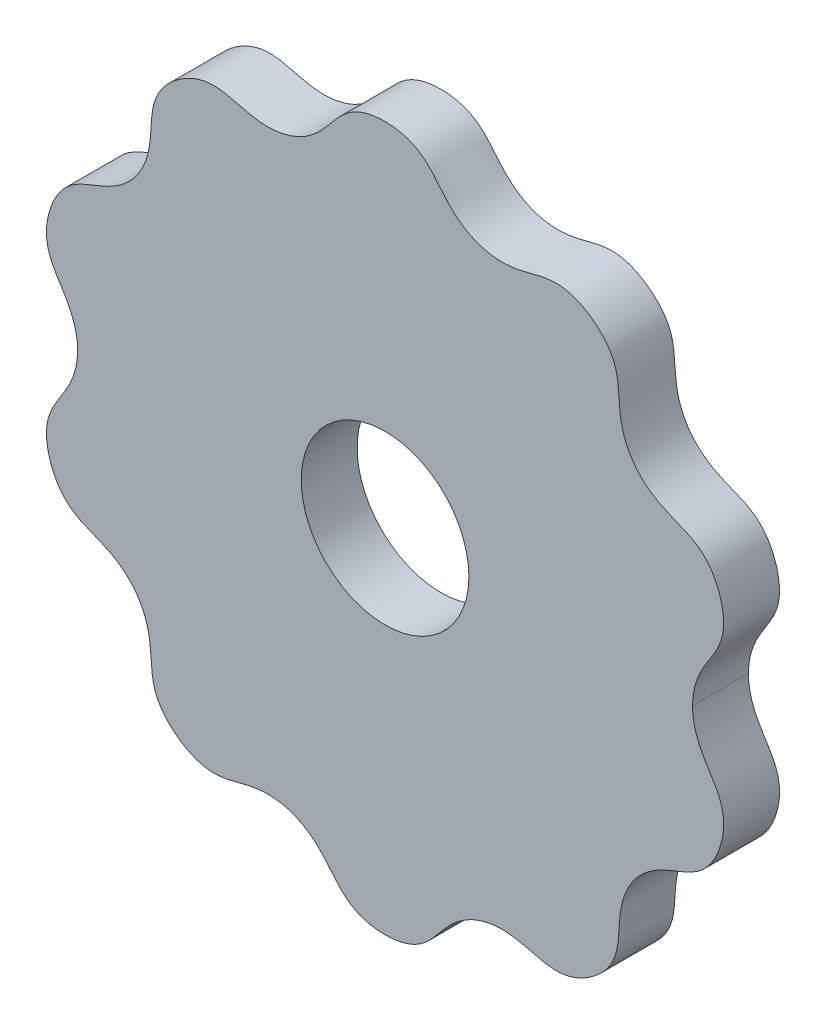
SolidWorks part; units mm, degrees
ref_plane "Front Plane" through (0, 0, 0) normal (0, 0, 1) x (1, 0, 0)
ref_plane "Top Plane" through (0, 0, 0) normal (0, 1, 0) x (1, 0, 0)
ref_plane "Right Plane" through (0, 0, 0) normal (1, 0, 0) x (0, 0, -1)
ref_plane "Plane1" through (0, 0, 4) normal (0, 0, 1) x (1, 0, 0)
sketch "Sketch1" plane through (0, 0, 4) normal (0, 0, 1) x (1, 0, 0)
  circle A0 centre (2, 0) radius 7.5
  spline S0 degree 5 poles (-25.5, 0) (-25.5, -0.5526) (-25.5746, -1.2434) (-25.8433, -2.3258) (-26.4239, -3.4504) (-27.2187, -4.6153) (-27.7942, -5.5576) (-28.2658, -6.8109) (-28.3864, -8.0323) (-28.1314, -9.4768) (-27.5806, -10.8552) (-26.8549, -11.8769) (-25.9559, -12.6827) (-24.9982, -13.1882) (-23.6912, -13.6755) (-22.3709, -14.191) (-20.8872, -15.2385) (-19.911, -16.4449) (-19.1799, -18.1084) (-18.9673, -19.4985) (-18.9256, -20.9082) (-18.8373, -22.0088) (-18.4822, -23.2999) (-17.8618, -24.3589) (-16.8065, -25.3777) (-15.5506, -26.1691) (-14.3631, -26.5691) (-13.162, -26.6926) (-12.0902, -26.5386) (-10.7464, -26.1646) (-9.3752, -25.8057) (-7.5591, -25.7809) (-6.0603, -26.1832) (-4.491, -27.0993) (-3.5019, -28.0989) (-2.6396, -29.2148) (-1.9213, -30.0534) (-0.8751, -30.8892) (0.2493, -31.3813) (1.7019, -31.5852) (3.183, -31.4872) (4.3789, -31.1128) (5.4232, -30.5068) (6.1999, -29.7522) (7.0672, -28.6597) (7.9654, -27.5634) (9.4202, -26.4759) (10.8692, -25.9204) (12.6772, -25.7391) (14.065, -25.9665) (15.4185, -26.3624) (16.4925, -26.6186) (17.8302, -26.6798) (19.0291, -26.417) (20.3241, -25.7282) (21.4648, -24.7783) (22.2122, -23.7725) (22.7008, -22.6684) (22.8857, -21.6014) (22.9452, -20.2078) (23.0275, -18.7929) (23.5652, -17.058) (24.4109, -15.7569) (25.7671, -14.5475) (27.0235, -13.9157) (28.3512, -13.4404) (29.3707, -13.0164) (30.4889, -12.2797) (31.3044, -11.3624) (31.9472, -10.0439) (32.3117, -8.605) (32.3252, -7.3519) (32.0715, -6.1715) (31.5938, -5.1996) (30.8229, -4.0372) (30.0578, -2.8441) (29.653, -1.6536) (29.5187, -0.829) (29.5, -0.1382) (29.5, 0) knots 0.5 0.5 0.5 0.5 0.5 0.5 0.513333 0.516667 0.526667 0.53 0.533333 0.54 0.55 0.556667 0.563333 0.566667 0.57 0.58 0.583333 0.596667 0.6 0.613333 0.616667 0.626667 0.63 0.633333 0.64 0.65 0.656667 0.663333 0.666667 0.67 0.68 0.683333 0.696667 0.7 0.713333 0.716667 0.726667 0.73 0.733333 0.74 0.75 0.756667 0.763333 0.766667 0.77 0.78 0.783333 0.796667 0.8 0.813333 0.816667 0.826667 0.83 0.833333 0.84 0.85 0.856667 0.863333 0.866667 0.87 0.88 0.883333 0.896667 0.9 0.913333 0.916667 0.926667 0.93 0.933333 0.94 0.95 0.956667 0.963333 0.966667 0.97 0.98 0.983333 0.996667 1 1 1 1 1 1 weights 1 1 1 1 1 1 1 1 1 1 1 1 1 1 1 1 1 1 1 1 1 1 1 1 1 1 1 1 1 1 1 1 1 1 1 1 1 1 1 1 1 1 1 1 1 1 1 1 1 1 1 1 1 1 1 1 1 1 1 1 1 1 1 1 1 1 1 1 1 1 1 1 1 1 1 1 1 1 1 1
  spline S1 degree 5 poles (29.5, 0) (29.5, 0.5526) (29.5746, 1.2434) (29.8433, 2.3258) (30.4239, 3.4504) (31.2187, 4.6153) (31.7942, 5.5576) (32.2658, 6.8109) (32.3864, 8.0323) (32.1314, 9.4768) (31.5806, 10.8552) (30.8549, 11.8769) (29.9559, 12.6827) (28.9982, 13.1882) (27.6912, 13.6755) (26.3709, 14.191) (24.8872, 15.2385) (23.911, 16.4449) (23.1799, 18.1084) (22.9673, 19.4985) (22.9256, 20.9082) (22.8373, 22.0088) (22.4822, 23.2999) (21.8618, 24.3589) (20.8065, 25.3777) (19.5506, 26.1691) (18.3631, 26.5691) (17.162, 26.6926) (16.0902, 26.5386) (14.7464, 26.1646) (13.3752, 25.8057) (11.5591, 25.7809) (10.0603, 26.1832) (8.491, 27.0993) (7.5019, 28.0989) (6.6396, 29.2148) (5.9213, 30.0534) (4.8751, 30.8892) (3.7507, 31.3813) (2.2981, 31.5852) (0.817, 31.4872) (-0.3789, 31.1128) (-1.4232, 30.5068) (-2.1999, 29.7522) (-3.0672, 28.6597) (-3.9654, 27.5634) (-5.4202, 26.4759) (-6.8692, 25.9204) (-8.6772, 25.7391) (-10.065, 25.9665) (-11.4185, 26.3624) (-12.4925, 26.6186) (-13.8302, 26.6798) (-15.0291, 26.417) (-16.3241, 25.7282) (-17.4648, 24.7783) (-18.2122, 23.7725) (-18.7008, 22.6684) (-18.8857, 21.6014) (-18.9452, 20.2078) (-19.0275, 18.7929) (-19.5652, 17.058) (-20.4109, 15.7569) (-21.7671, 14.5475) (-23.0235, 13.9157) (-24.3512, 13.4404) (-25.3707, 13.0164) (-26.4889, 12.2797) (-27.3044, 11.3624) (-27.9472, 10.0439) (-28.3117, 8.605) (-28.3252, 7.3519) (-28.0715, 6.1715) (-27.5938, 5.1996) (-26.8229, 4.0372) (-26.0578, 2.8441) (-25.653, 1.6536) (-25.5187, 0.829) (-25.5, 0.1382) (-25.5, 0) knots 0 0 0 0 0 0 0.013333 0.016667 0.026667 0.03 0.033333 0.04 0.05 0.056667 0.063333 0.066667 0.07 0.08 0.083333 0.096667 0.1 0.113333 0.116667 0.126667 0.13 0.133333 0.14 0.15 0.156667 0.163333 0.166667 0.17 0.18 0.183333 0.196667 0.2 0.213333 0.216667 0.226667 0.23 0.233333 0.24 0.25 0.256667 0.263333 0.266667 0.27 0.28 0.283333 0.296667 0.3 0.313333 0.316667 0.326667 0.33 0.333333 0.34 0.35 0.356667 0.363333 0.366667 0.37 0.38 0.383333 0.396667 0.4 0.413333 0.416667 0.426667 0.43 0.433333 0.44 0.45 0.456667 0.463333 0.466667 0.47 0.48 0.483333 0.496667 0.5 0.5 0.5 0.5 0.5 0.5 weights 1 1 1 1 1 1 1 1 1 1 1 1 1 1 1 1 1 1 1 1 1 1 1 1 1 1 1 1 1 1 1 1 1 1 1 1 1 1 1 1 1 1 1 1 1 1 1 1 1 1 1 1 1 1 1 1 1 1 1 1 1 1 1 1 1 1 1 1 1 1 1 1 1 1 1 1 1 1 1 1
extrude "Boss-Extrude1" add sketch "Sketch1" along normal blind 5
